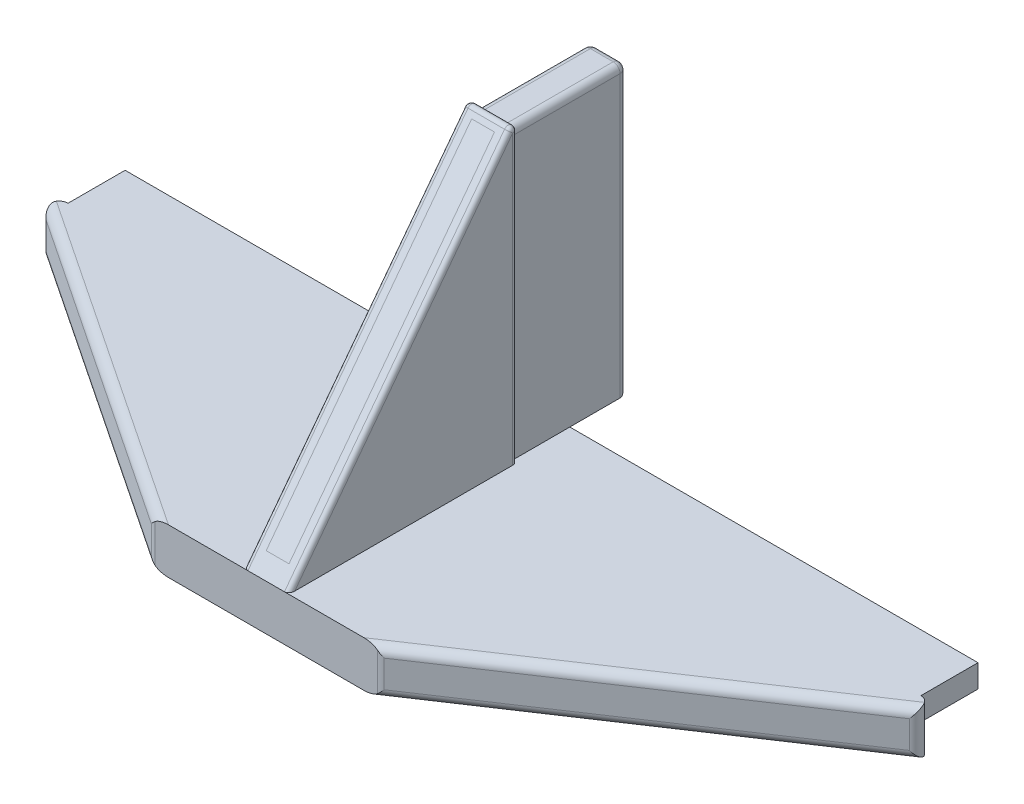
SolidWorks part; units mm, degrees
ref_plane "Front Plane" through (0, 0, 0) normal (0, 0, 1) x (1, 0, 0)
ref_plane "Top Plane" through (0, 0, 0) normal (0, 1, 0) x (1, 0, 0)
ref_plane "Right Plane" through (0, 0, 0) normal (1, 0, 0) x (0, 0, -1)
sketch "Sketch4" plane through (0, 0, 0) normal (0, 1, 0) x (1, 0, 0)
  line L0 (0, 0) -> (100, 0)
  line L1 (50, 100) -> (250, 100)
  line L2 (50, 100) -> (-150, 100)
  line L3 (-150, 100) -> (0, 0)
  line L4 (100, 0) -> (250, 100)
  line L5 (50, 90) -> (-116.9722, 90)
  line L6 (-116.9722, 90) -> (3.0278, 10)
  line L7 (3.0278, 10) -> (96.9722, 10)
  line L8 (96.9722, 10) -> (216.9722, 90)
  line L9 (50, 90) -> (216.9722, 90)
  point P3 (50, 0)
  point P4 (50, 100)
  dimension "D1" = 100
  dimension "D2" = 100
  dimension "D3" = 200
  dimension "D4" = 200
  dimension "D5" = 10
extrude "Boss-Extrude2" add sketch "Sketch4" along normal blind 20
fillet "Fillet8" radius 4 8 edges at (-150, 10, -100) (-75, 0, -50) (-75, 20, -50) (0, 10, 0) (250, 10, -100) (100, 10, 0) (175, 0, -50) (175, 20, -50)
sketch "Sketch5" plane through (0, 20, 0) normal (0, 1, 0) x (1, 0, 0)
  line L0 (7.2111, 0) -> (92.7889, 0) construction
  line L1 (60, 0) -> (60, 100)
  line L2 (236.7889, 100) -> (-136.7889, 100) construction
  line L3 (40, 0) -> (40, 100)
  line L4 (60, 0) -> (40, 0)
  line L5 (60, 100) -> (40, 100)
  line L6 (45, 5) -> (45, 95)
  line L7 (55, 95) -> (45, 95)
  line L8 (55, 5) -> (55, 95)
  line L9 (55, 5) -> (45, 5)
  point P0 (50, 0)
  dimension "D1" = 20
  dimension "D2" = 10
  dimension "D3" = 5
extrude "Boss-Extrude3" add sketch "Sketch5" along normal blind 132
sketch "Sketch6" plane through (60, 0, 0) normal (1, 0, 0) x (0, 0, -1)
  line L0 (0, 20) -> (100, 152)
  line L1 (0, 152) -> (100, 152)
  line L2 (0, 152) -> (0, 20)
extrude "Cut-Extrude1" cut sketch "Sketch6" against normal blind 132
fillet "Fillet9" radius 2 5 edges at (60, 86, -100) (40, 86, -100) (60, 86, -50) (40, 86, -50) (50, 152, -100)
sketch "Sketch7" plane through (0, 20, 0) normal (0, 1, 0) x (1, 0, 0)
  line L0 (236.7889, 100) -> (-136.7889, 100)
  line L1 (236.7889, 100) -> (236.7889, 125)
  line L2 (-136.7889, 100) -> (-136.7889, 125)
  line L3 (236.7889, 125) -> (-136.7889, 125)
  dimension "D1" = 25
extrude "Boss-Extrude4" add sketch "Sketch7" against normal blind 10 separate body
ref_plane "Plane2" through (58, 0, 0) normal (1, 0, 0) x (0, 0, -1)
sketch "Sketch8" plane through (58, 0, 0) normal (1, 0, 0) x (0, 0, -1)
  line L0 (100, 20) -> (100, 146.048)
  line L1 (100, 20) -> (150, 20)
  line L2 (100, 146.048) -> (150, 146.048)
  line L3 (150, 20) -> (150, 146.048)
  dimension "D1" = 50
extrude "Boss-Extrude5" add sketch "Sketch8" against normal up to vertex (16 mm away) up to point (42, 146.048, -100)
fillet "Fillet12" radius 3 6 edges at (50, 20, -150) (50, 146.048, -150) (42, 83.024, -150) (58, 83.024, -150) (42, 146.048, -125) (58, 146.048, -125)
extrude "Boss-Extrude6" add sketch "Sketch4<2>" along normal blind 3 contours L9 L5 L6 L7 L8 region at (50, 0, -57.4786)
sketch "Sketch4<2>" plane through (0, 0, 0) normal (0, 1, 0) x (1, 0, 0) same geometry as "Sketch4"
extrude "Boss-Extrude7" add sketch "Sketch4<3>" along normal blind 3 from offset 17 contours L9 L5 L6 L7 L8 region at (50, 0, -57.4786)
sketch "Sketch4<3>" plane through (0, 0, 0) normal (0, 1, 0) x (1, 0, 0) same geometry as "Sketch4"
sketch "Sketch9" plane through (0, 7.2929, 9.6266) normal (0, 0.6039, 0.7971) x (1, 0, 0)
  line L0 (55, 24.2219) -> (45, 24.2219) construction
  line L1 (55, 173.2637) -> (55, 24.2219) construction
  line L2 (45, 24.2219) -> (45, 173.2637) construction
  line L3 (45, 173.2637) -> (55, 173.2637) construction
  line L4 (42, 15.9418) -> (58, 15.9418)
  line L5 (58, 15.9418) -> (58, 175.5917)
  line L6 (58, 175.5917) -> (42, 175.5917)
  line L7 (42, 175.5917) -> (42, 15.9418)
  line L8 (42, 15.9418) -> (58, 15.9418)
  line L9 (58, 15.9418) -> (58, 175.5917)
  line L10 (58, 175.5917) -> (42, 175.5917)
  line L11 (42, 175.5917) -> (42, 15.9418)
  line L12 (55, 24.2219) -> (45, 24.2219)
  line L13 (55, 173.2637) -> (55, 24.2219)
  line L14 (45, 24.2219) -> (45, 173.2637)
  line L15 (45, 173.2637) -> (55, 173.2637)
  line M13 (55, 24.2219) -> (45, 24.2219)
  line M14 (45, 24.2219) -> (45, 173.2637)
  line M15 (45, 173.2637) -> (55, 173.2637)
  line M16 (55, 173.2637) -> (55, 24.2219)
  dimension "D1" = 0
extrude "Boss-Extrude8" add sketch "Sketch9" against normal blind 3 separate body contours M13 M16 M15 M14 region at (50, 86, -50)
